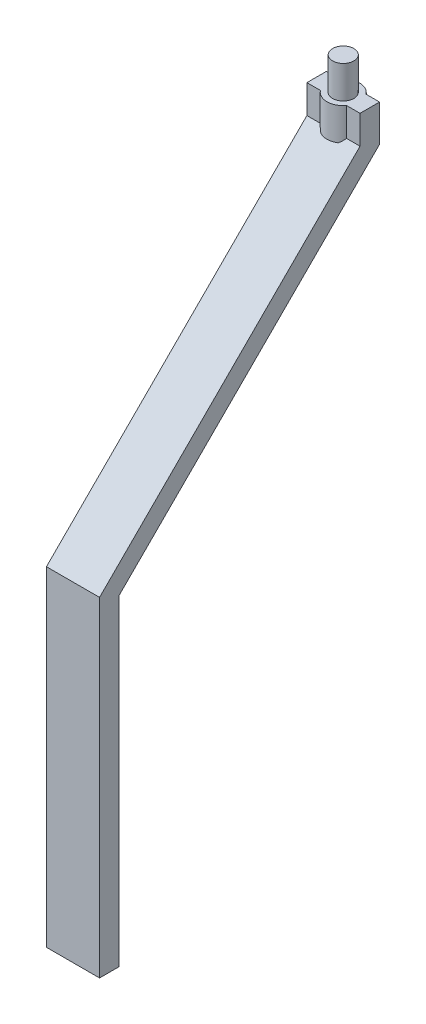
SolidWorks part; units mm, degrees
material "6063-T5"
ref_plane "Front Plane" through (0, 0, 0) normal (0, 0, 1) x (1, 0, 0)
ref_plane "Top Plane" through (0, 0, 0) normal (0, 1, 0) x (1, 0, 0)
ref_plane "Right Plane" through (0, 0, 0) normal (1, 0, 0) x (0, 0, -1)
sketch "Sketch1" plane through (0, 0, 0) normal (0, 1, 0) x (1, 0, 0)
  circle A0 centre (0, 0) radius 8.2
  dimension "D1" = 16.4
extrude "Boss-Extrude1" add sketch "Sketch1" along normal blind 25 contours A0
sketch "Sketch2" plane through (0, 0, 0) normal (0, -1, 0) x (-1, 0, 0)
  line L0 (-20.395, -7.5) -> (20.395, -7.5)
  line L1 (-20.395, -7.5) -> (-20.395, 7.5)
  line L2 (20.395, -7.5) -> (20.395, 7.5)
  line L3 (-20.395, 7.5) -> (20.395, 7.5)
  line L4 (-20.395, -7.5) -> (20.395, 7.5) construction
  line L5 (20.395, -7.5) -> (-20.395, 7.5) construction
  point P1 (0, 0)
  dimension "D1" = 40.79
  dimension "D2" = 15
extrude "Boss-Extrude2" add sketch "Sketch2" along normal blind 25
sketch "Sketch3" plane through (0, -25, 0) normal (0, -1, 0) x (-1, 0, 0)
  circle A0 centre (0, 0) radius 12.5
  dimension "D1" = 25
extrude "Boss-Extrude4" add sketch "Sketch3" against normal up to surface (25 mm away) up to face at (-13.0763, 0, 0)
sketch "Sketch4" plane through (-20.395, 0, 0) normal (-1, 0, 0) x (0, 0, 1)
  line L0 (7.5, -25) -> (207.5, -25)
  line L1 (207.5, -25) -> (207.5, -225)
  line L2 (207.5, -225) -> (7.5, -25)
  line L3 (207.5, -225) -> (192.5, -225)
  line L5 (192.5, -225) -> (-7.5, -25)
  line L6 (-7.5, -25) -> (7.5, -25)
  line M7 (-7.5, -25) -> (7.5, -25)
  dimension "D1" = 200
  dimension "D2" = 200
  dimension "D3" = 15
extrude "Boss-Extrude5" add sketch "Sketch4" against normal up to surface (40.79 mm away) contours L5 L3 L2 M7 region at (-20.395, -125, 100) up to face at (20.395, -12.5, 0)
sketch "Sketch5" plane through (0, -225, 0) normal (0, -1, 0) x (-1, 0, 0)
  line L1 (-20.395, -207.5) -> (20.395, -207.5)
  line L2 (-20.395, -207.5) -> (-20.395, -192.5)
  line L3 (-20.395, -192.5) -> (20.395, -192.5)
  line L4 (20.395, -207.5) -> (20.395, -192.5)
extrude "Boss-Extrude7" add sketch "Sketch5" along normal blind 1505
sketch "Sketch7" plane through (20.395, 0, 0) normal (1, 0, 0) x (0, 0, -1)
  line L0 (-7.5, -25) -> (0, -32.5)
  line L1 (7.5, -25) -> (-192.5, -225) construction
  line L2 (0, -32.5) -> (1.5521, -34.0521)
  line L3 (-7.5, -25) -> (-9.0521, -23.4479)
  line L4 (-9.0521, -23.4479) -> (-7.5, -21.8958)
  line L5 (-7.5, -25) -> (-7.5, 0) construction
  line L6 (1.5521, -34.0521) -> (7.5, -28.1042)
  line L7 (7.5, -28.1042) -> (7.5, -25)
  line L8 (1.5521, -34.0521) -> (-192.5, -228.1042)
  line L9 (-192.5, -1730) -> (-192.5, -225) construction
  line L10 (-192.5, -228.1042) -> (-192.5, -225)
  line L11 (-192.5, -225) -> (7.5, -25)
  line L12 (-9.0521, -23.4479) -> (-207.5, -221.8958)
  line L13 (-207.5, -221.8958) -> (-207.5, -225)
  line L14 (-207.5, -225) -> (-7.5, -25)
  line L15 (-7.5, -21.8958) -> (-7.5, -25)
  line M3 (-7.5, 0) -> (-7.5, -25)
  line M4 (-7.5, -25) -> (-207.5, -225)
  line M6 (-192.5, -225) -> (7.5, -25)
  line M12 (-192.5, -1730) -> (-192.5, -225)
  dimension "D1" = 10.6066
  dimension "D2" = 2.195
  dimension "D3" = 2.195
extrude "Boss-Extrude8" add sketch "Sketch7" against normal up to surface (40.79 mm away) contours L8 L2 M6 M12 | L6 L7 L2 M6 | L12 L13 L3 M4 | L4 L3 M3 region at (20.395, -29.8693, -4.1231) region at (20.395, -129.9156, 95.8615) region at (20.395, -123.8374, 107.8875) region at (20.395, -23.4479, 8.0174) up to face at (-20.395, -495, 100)
ref_plane "Plane4" through (0, 0, 0) normal (1, 0, 0) x (0, 0, -1)
ref_axis "Axis1" through (0, -1730, 192.5) along (0, 0, 1)
sketch "Sketch9" plane through (0, 0, 0) normal (1, 0, 0) x (0, 0, -1)
  line L0 (0, 0) -> (0, -1530)
  line L1 (0, -1530) -> (-200, -1530)
  line L2 (-200, -1530) -> (-200, -1515)
  line L3 (-200, -1515) -> (-185, -1515)
  line L4 (-200, -1530) -> (-215, -1530)
  line L5 (-215, -1530) -> (-215, -1545)
  line L7 (-215, -1545) -> (-185, -1545)
  line L8 (-215, -1545) -> (-215, -1515)
  line L9 (-215, -1515) -> (-185, -1515)
  line L10 (-185, -1545) -> (-185, -1515)
  dimension "D1" = 1530
  dimension "D2" = 200
  dimension "D3" = 15
  dimension "D4" = 15
  dimension "D5" = 15
  dimension "D6" = 15
revolve "Revolve1" add sketch "Sketch9" angle 60 about axis through (0, -1730, 192.5) along (0, 0, 1) region at (0, -1537.5, 200) region at (0, -1522.5, 192.5) region at (0, -1522.5, 207.5) other way angle 60
fillet "Fillet3" radius 50 4 edges at (20.395, -1515.9695, 200) (-20.395, -1515.9695, 200) (0, -1515, 192.5) (0, -1515, 207.5) type face fillet first side face at (0, -1568.75, 200) second side face at (-20.395, -441.4924, 100) second side face at (0, -868.6903, 207.5) second side face at (20.395, -441.4924, 100) second side face at (0, -871.7945, 192.5)
sketch "Sketch11" plane through (749.112, -1297.5, 0) normal (0.5, -0.866, 0) x (-0.866, -0.5, 0)
  line L0 (665, -185) -> (665, -215)
  line L1 (680, -185) -> (650, -185) construction
  line L2 (680, -215) -> (650, -215) construction
  line L3 (627.5, -237.5) -> (702.5, -237.5)
  line L4 (627.5, -237.5) -> (627.5, -162.5)
  line L5 (702.5, -237.5) -> (702.5, -162.5)
  line L6 (627.5, -162.5) -> (702.5, -162.5)
  line L7 (627.5, -237.5) -> (702.5, -162.5) construction
  line L8 (702.5, -237.5) -> (627.5, -162.5) construction
  line L9 (665, -200) -> (650, -185)
  line L10 (650, -185) -> (627.5, -162.5)
  circle A0 centre (638.75, -173.75) radius 4
  circle A1 centre (691.25, -173.75) radius 4
  circle A2 centre (691.25, -226.25) radius 4
  circle A3 centre (638.75, -226.25) radius 4
  point P7 (665, -200)
  point P25 (665, -200)
  line M1 (650, -185) -> (650, -215)
  line M2 (650, -215) -> (680, -215)
  line M3 (680, -215) -> (680, -185)
  line M4 (680, -185) -> (650, -185)
  dimension "D3" = 8
  dimension "D1" = 75
  dimension "D2" = 75
  dimension "D4" = 4
extrude "Boss-Extrude9" add sketch "Sketch11" against normal blind 30 contours A0 L4 L3 L5 L6 A3 A2 A1 M4 M3 M2 M1 | L0 L9 M1 M2 | L9 L0 M4 | L0 M4 M2 M3 region at (166.7099, -1633.75, 200) region at (173.2051, -1630, 163.5607) region at (177.5352, -1627.5, 190) region at (180.422, -1625.8333, 203.3333)
mirror "Mirror1" about plane through (0, 0, 0) normal (1, 0, 0) of "Boss-Extrude9"
sketch "Sketch15" plane through (0, 0, 192.5) normal (0, 0, -1) x (-1, 0, 0)
  line L0 (-20.395, -1730) -> (-20.395, -1546.1276)
  line L1 (20.395, -1546.1276) -> (20.395, -1730)
  line L2 (20.395, -1730) -> (-20.395, -1730)
  arc A0 (-20.395, -1546.1276) -> (20.395, -1546.1276) centre (0, -1730) cw
extrude "Cut-Extrude2" cut sketch "Sketch15" against normal through all
ref_plane "Plane5" through (0, -975, 0) normal (0, 1, 0) x (1, 0, 0)
sketch "Sketch16" plane through (0, -975, 0) normal (0, 1, 0) x (1, 0, 0)
  circle A0 centre (0, 0) radius 558.4075
extrude "Cut-Extrude3" cut sketch "Sketch16" against normal through all and the other way blind 500
